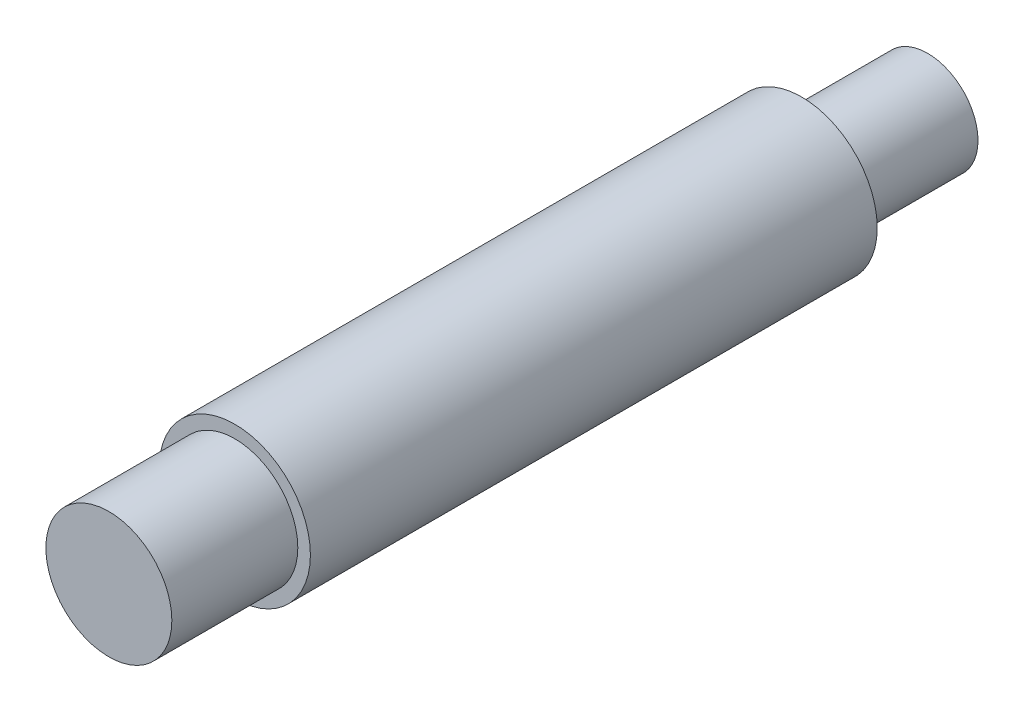
SolidWorks part; units mm, degrees
material "1060 Alloy"
ref_plane "Front Plane" through (0, 0, 0) normal (0, 0, 1) x (1, 0, 0)
ref_plane "Top Plane" through (0, 0, 0) normal (0, 1, 0) x (1, 0, 0)
ref_plane "Right Plane" through (0, 0, 0) normal (1, 0, 0) x (0, 0, -1)
sketch "Sketch6" plane through (0, 0, 0) normal (1, 0, 0) x (0, 0, -1)
  line L0 (0, 0) -> (65, 0)
  line L1 (65, 0) -> (65, 4)
  line L2 (65, 4) -> (55, 4)
  line L3 (55, 4) -> (55, 6)
  line L4 (55, 6) -> (10, 6)
  line L5 (10, 6) -> (10, 5)
  line L6 (10, 5) -> (0, 5)
  line L7 (0, 5) -> (0, 0)
  dimension "D1" = 10
  dimension "D2" = 5
  dimension "D3" = 6
  dimension "D4" = 45
  dimension "D5" = 4
revolve "Revolve1" add sketch "Sketch6" angle 360 about L0
